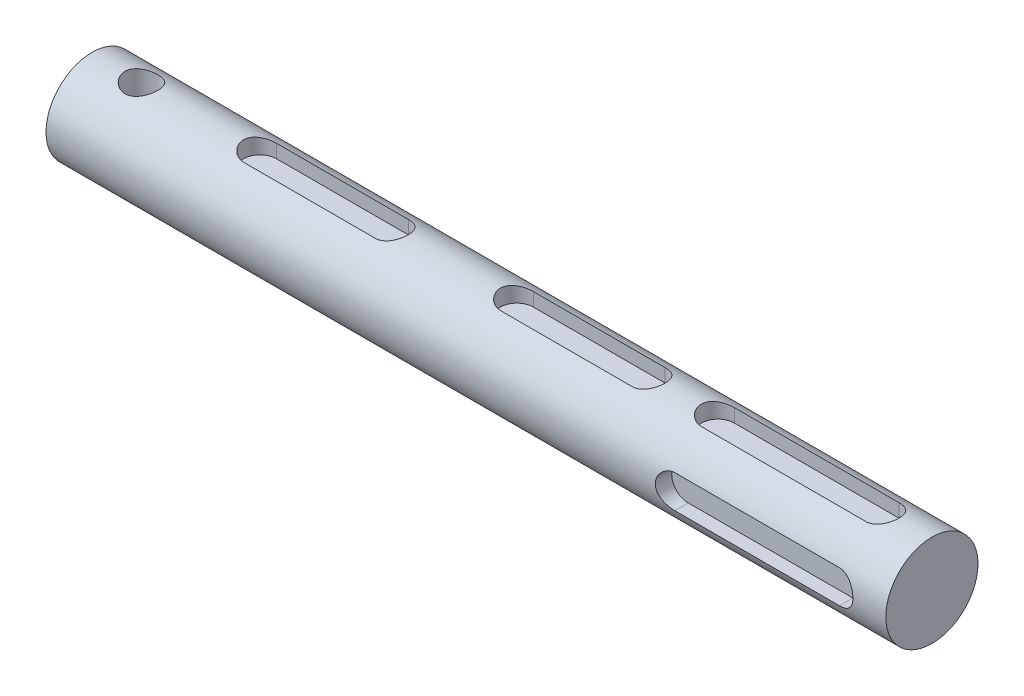
SolidWorks part; units mm, degrees
ref_plane "Front Plane" through (0, 0, 0) normal (0, 0, 1) x (1, 0, 0)
ref_plane "Top Plane" through (0, 0, 0) normal (0, 1, 0) x (1, 0, 0)
ref_plane "Right Plane" through (0, 0, 0) normal (1, 0, 0) x (0, 0, -1)
sketch "Sketch1" plane through (0, 0, 0) normal (1, 0, 0) x (0, 0, -1)
  circle A0 centre (0, 0) radius 7
  dimension "D1" = 14
extrude "Boss-Extrude1" add sketch "Sketch1" along normal mid plane 70
ref_plane "Plane1" through (0, 7, 0) normal (0, 1, 0) x (1, 0, 0)
sketch "Sketch4" plane through (0, 7, 0) normal (0, 1, 0) x (1, 0, 0)
  line L0 (-29.5, 0) -> (-9.5, 0) construction
  line L1 (-29.5, 2.5) -> (-9.5, 2.5)
  line L2 (-29.5, -2.5) -> (-9.5, -2.5)
  arc A0 (-29.5, 2.5) -> (-29.5, -2.5) centre (-29.5, 0) ccw
  arc A1 (-9.5, -2.5) -> (-9.5, 2.5) centre (-9.5, 0) ccw
  point P3 (-19.5, 0)
  dimension "D2" = 2.5
  dimension "D1" = 20
  dimension "D3" = 9.5
extrude "Cut-Extrude1" cut sketch "Sketch4" against normal blind 2.5
mirror "Mirror1" about plane through (0, 0, 0) normal (1, 0, 0) of "Cut-Extrude1"
sketch "Sketch5" plane through (-35, 0, 0) normal (-1, 0, 0) x (0, 0, 1)
  circle A1 centre (0, 0) radius 7
  circle A2 centre (0, 0) radius 7
  dimension "D1" = 0
extrude "Boss-Extrude3" add sketch "Sketch5" along normal blind 20
sketch "Sketch6" plane through (0, 0, 0) normal (0, 1, 0) x (1, 0, 0)
  line L0 (-55, 7) -> (-55, -7) construction
  line L1 (-47.5, 0) -> (-55, 0) construction
  circle A0 centre (-47.5, 0) radius 2.5
  dimension "D1" = 5
  dimension "D2" = 7.5
extrude "Cut-Extrude2" cut sketch "Sketch6" against normal through all both and the other way through all
sketch "Sketch7" plane through (35, 0, 0) normal (1, 0, 0) x (0, 0, -1)
  circle A2 centre (0, 0) radius 7
  dimension "D1" = 14
extrude "Boss-Extrude4" add sketch "Sketch7" along normal blind 37.5
sketch "Sketch9" plane through (0, 7, 0) normal (0, 1, 0) x (1, 0, 0)
  line L0 (40, 0) -> (65, 0) construction
  line L1 (40, 2.5) -> (65, 2.5)
  line L2 (40, -2.5) -> (65, -2.5)
  line L3 (65, 0) -> (72.5, 0) construction
  line L4 (72.5, -7) -> (72.5, 7) construction
  arc A0 (40, 2.5) -> (40, -2.5) centre (40, 0) ccw
  arc A1 (65, -2.5) -> (65, 2.5) centre (65, 0) ccw
  point P3 (52.5, 0)
  dimension "D1" = 2.5
  dimension "D2" = 25
  dimension "D3" = 7.5
extrude "Cut-Extrude3" cut sketch "Sketch9" against normal blind 2.5
ref_plane "Plane2" through (0, 0, 7) normal (0, 0, 1) x (1, 0, 0)
sketch "Sketch10" plane through (0, 0, 7) normal (0, 0, 1) x (1, 0, 0)
  line L0 (40, 0) -> (65, 0) construction
  line L1 (40, 2.5) -> (65, 2.5)
  line L2 (40, -2.5) -> (65, -2.5)
  line L3 (72.5, -7) -> (72.5, 7) construction
  arc A0 (40, 2.5) -> (40, -2.5) centre (40, 0) ccw
  arc A1 (65, -2.5) -> (65, 2.5) centre (65, 0) ccw
  point P3 (52.5, 0)
  dimension "D1" = 2.5
  dimension "D2" = 25
  dimension "D3" = 7.5
extrude "Cut-Extrude4" cut sketch "Sketch10" against normal blind 2.5
